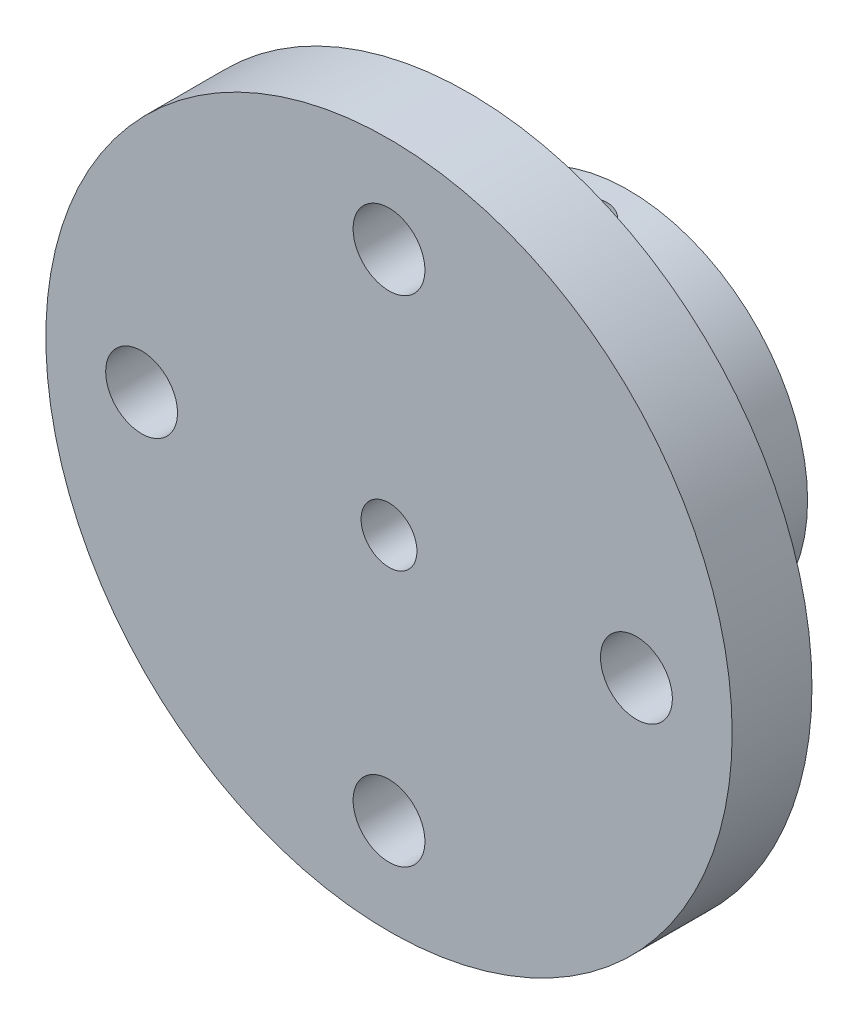
SolidWorks part; units mm, degrees
material "ABS"
ref_plane "Front Plane" through (0, 0, 0) normal (0, 0, 1) x (1, 0, 0)
ref_plane "Top Plane" through (0, 0, 0) normal (0, 1, 0) x (1, 0, 0)
ref_plane "Right Plane" through (0, 0, 0) normal (1, 0, 0) x (0, 0, -1)
sketch "Sketch1" plane through (0, 0, 0) normal (1, 0, 0) x (0, 0, -1)
  line L0 (-486.8485, 0) -> (23855.5787, 0) construction
  line L1 (0, 21.5) -> (5, 21.5)
  line L2 (5, 21.5) -> (9, 11.225)
  line L3 (9, 11.225) -> (15, 11.225)
  line L4 (15, 11.225) -> (15, 3.225)
  line L5 (15, 3.225) -> (0, 3.225)
  line L6 (0, 3.225) -> (0, 21.5)
  line L7 (0, 15.5) -> (7.3358, 15.5) construction
  dimension "D1" = 5
  dimension "D2" = 6.45
  dimension "D3" = 8
  dimension "D4" = 6
  dimension "D5" = 4
  dimension "D6" = 6
  dimension "D7" = 15.5
revolve "Revolve1" add sketch "Sketch1" angle 360 about L0
ref_plane "Plane1" through (0, 0, -9) normal (0, 0, 1) x (1, 0, 0)
sketch "Sketch11" plane through (0, 0, 0) normal (0, 0, 1) x (1, 0, 0)
  circle A0 centre (0, 0) radius 3.225
  circle A2 centre (0, 0) radius 3.225 construction
  circle A3 centre (0, 0) radius 1.75
  dimension "D1" = 3.5
extrude "Boss-Extrude2" add sketch "Sketch11" against normal blind 7
hole_wizard "CBORE for M4 SHCS1" positions "Sketch3" profile "Sketch4" counterbore size "M4" standard "ANSI Metric" end condition through all
sketch "Sketch3" plane through (0, 0, -9) normal (0, 0, 1) x (1, 0, 0)
  point P0 (0, 15.5)
sketch "Sketch4" plane through (0, 15.5, -9) normal (1, 0, 0) x (0, 1, 0)
  line L0 (0, 0) -> (0, 9)
  line L1 (0, 9) -> (2.25, 9)
  line L3 (2.25, 9) -> (2.25, 4)
  line L4 (2.25, 4) -> (4, 4)
  line L5 (4, 4) -> (4, 0)
  line L7 (4, 0) -> (0, 0)
  line L11 (0, -6.35) -> (0, 107.95) construction
  dimension "Thru Hole Dia." = 4.5
  dimension "Thru Hole Depth" = 9
  dimension "C'Bore Dia." = 8
  dimension "C'Bore Depth" = 4
pattern_circular "CirPattern1" count 4 over 360 about axis through (0, 0, 486.8485) along (0, 0, 1) of "CBORE for M4 SHCS1" reverse direction yes
sketch "Sketch6" plane through (0, 0, 0) normal (0, 0, 1) x (1, 0, 0)
  line L0 (-1.5375, 2.8349) -> (1.5375, 2.8349)
  circle A0 centre (0, 0) radius 3.225 construction
  circle A1 centre (0, 0) radius 3.225
  dimension "D1" = 3.075
extrude "Boss-Extrude1" add sketch "Sketch6" against normal up to surface (15 mm away) contours L0 A1 region at (0, 2.9918, 0) up to face at (11.225, 0, -15)
sketch "Sketch8" plane through (0, 2.8349, 0) normal (0, -1, 0) x (1, 0, 0)
  line L0 (0, -15) -> (0, -12)
  line L1 (-11.225, -15) -> (11.225, -15) construction
  dimension "D1" = 3
hole_wizard "M4x0.7 Tapped Hole1" positions "Sketch9" profile "Sketch10" tap size "M4x0.7" standard "ANSI Metric" end condition through all
sketch "Sketch9" plane through (0, 0, 0) normal (0, -1, 0) x (-1, 0, 0)
  point P0 (0, 12)
cosmetic thread "Hole Thread3" parameters "D2"=4
sketch "Sketch10" plane through (0, 0, -12) normal (1, 0, 0) x (0, 0, -1)
  line L0 (0, 0) -> (0, 21.5)
  line L1 (0, 21.5) -> (1.65, 21.5)
  line L2 (1.65, 21.5) -> (1.65, 0)
  line L5 (1.65, 0) -> (0, 0)
  line L11 (0, -6.35) -> (0, 107.95) construction
  dimension "Thru Tap Drill Dia." = 3.3
  dimension "Thru Tap Drill Depth" = 21.5
pattern_circular "CirPattern2" count 2 every 120 about axis through (0, 0, 486.8485) along (0, 0, 1) of "M4x0.7 Tapped Hole1"
cosmetic thread "Hole Thread4" parameters "D2"=4
chamfer "Chamfer1" distance 2 angle 45 1 edges at (11.225, 0, -9) first distance on face at (-8.8154, -6.949, -12.3596)
